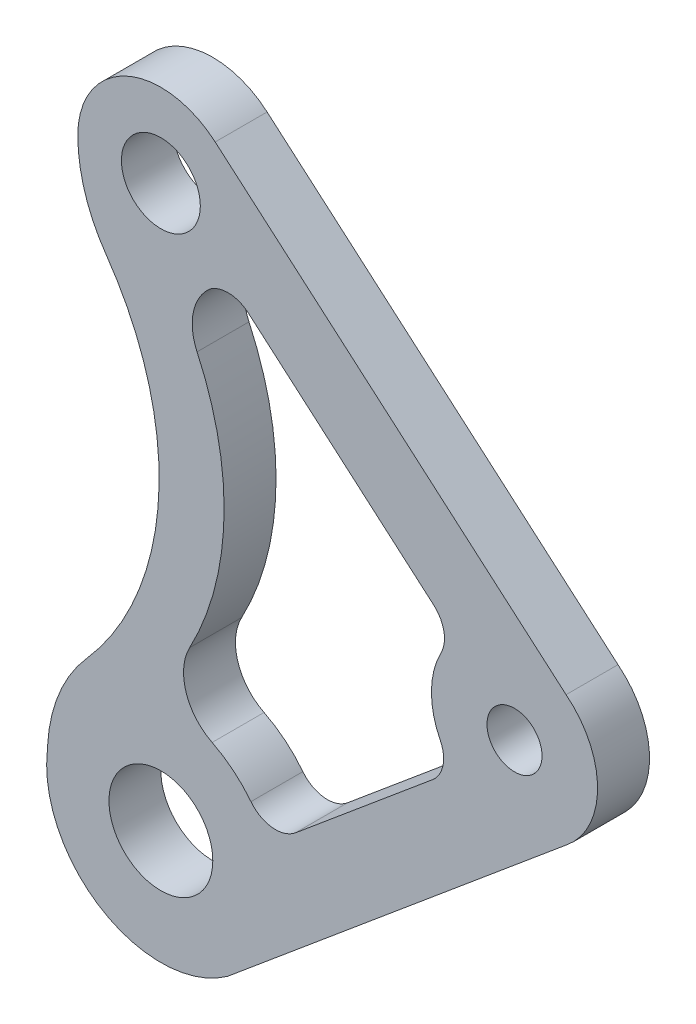
SolidWorks part; units mm, degrees
material "6061-T6 (SS)"
ref_plane "X-Y Datum" through (0, 0, 0) normal (0, 0, 1) x (1, 0, 0)
ref_plane "X-Z Datum" through (0, 0, 0) normal (0, 1, 0) x (1, 0, 0)
ref_plane "Y-Z Datum" through (0, 0, 0) normal (1, 0, 0) x (0, 0, -1)
sketch "Sketch1" plane through (0, 0, 0) normal (0, 0, 1) x (1, 0, 0)
  line L0 (0, 0) -> (0, 68.58) construction
  line L1 (0, 68.58) -> (43.2483, 31.2208) construction
  line L2 (43.2483, 31.2208) -> (0, 0) construction
  line L3 (-13.97, 0) -> (-10.16, 68.58)
  line L4 (6.6414, 76.2688) -> (49.5557, 39.1859)
  line L5 (49.5557, 23.2558) -> (8.1778, -11.3263)
  circle A0 centre (0, 0) radius 6.35
  circle A1 centre (43.2483, 31.2208) radius 3.3655
  circle A2 centre (0, 68.58) radius 4.826
  arc A3 (-10.16, 68.58) -> (6.6414, 76.2688) centre (0, 68.58) cw
  arc A4 (49.5557, 39.1859) -> (49.5557, 23.2558) centre (43.2483, 31.2208) cw
  arc A5 (8.1778, -11.3263) -> (-13.97, 0) centre (0, 0) cw
  point P16 (53.4083, 31.2208)
  dimension "D4" = 12.7
  dimension "D5" = 6.731
  dimension "D6" = 9.652
  dimension "D7" = 13.97
  dimension "D8" = 10.16
  dimension "D9" = 10.16
  dimension "D1" = 68.58
  dimension "D2" = 57.15
  dimension "D3" = 53.34
  dimension "D10" = 130.82
  dimension "D11" = 125.83
  dimension "D12" = 103.25
extrude "Boss-Extrude1" add sketch "Sketch1" along normal blind 6.35
sketch "Sketch2" plane through (0, 0, 6.35) normal (0, 0, 1) x (1, 0, 0)
  line L0 (-10.16, 68.58) -> (-13.97, 0) construction
  line L1 (-10.5128, 62.23) -> (-13.4408, 9.525)
  arc A0 (-10.5128, 62.23) -> (-13.4408, 9.525) centre (-35.7711, 37.1994) cw
  dimension "D3" = 35.56
  dimension "D1" = 6.35
  dimension "D2" = 9.525
extrude "Cut-Extrude1" cut sketch "Sketch2" against normal blind 6.35
fillet "Fillet1" radius 19.05 2 edges at (-10.5128, 62.23, 3.175) (-13.4408, 9.525, 3.175)
sketch "Sketch3" plane through (0, 0, 6.35) normal (0, 0, 1) x (1, 0, 0)
  line L2 (8.0877, 62.4306) -> (35.9845, 38.3245)
  line L3 (49.5557, 39.1859) -> (6.6414, 76.2688) construction
  line L6 (12.9992, 5.1168) -> (35.8725, 24.2335)
  arc A0 (35.9845, 38.3245) -> (35.8725, 24.2335) centre (43.2483, 31.2208) ccw
  arc A1 (-1.655, 13.8716) -> (12.9992, 5.1168) centre (0, 0) cw
  arc A3 (1.2017, 58.4913) -> (-1.655, 13.8716) centre (-27.8241, 37.9483) cw
  arc A6 (1.2017, 58.4913) -> (8.0877, 62.4306) centre (0, 68.58) ccw
  dimension "D1" = 10.16
  dimension "D2" = 10.16
  dimension "D3" = 13.97
  dimension "D6" = 6.7275
  dimension "D7" = 35.56
  dimension "D4" = 29.81
  dimension "D5" = 9.525
  dimension "D11" = 75.318
extrude "Cut-Extrude2" cut sketch "Sketch3" against normal blind 6.35
sketch3d "3DSketch1"
  line L0 (0, 68.58, 6.35) -> (0, 68.58, 0) construction
  line L1 (43.2483, 31.2208, 6.35) -> (43.2483, 31.2208, 0) construction
  point P0 (0, 68.58, 6.35)
  point P1 (43.2483, 31.2208, 6.35)
fillet "Fillet2" radius 3.81 4 edges at (35.9845, 38.3245, 3.175) (12.9992, 5.1168, 3.175) (35.8725, 24.2335, 3.175) (8.0877, 62.4306, 3.175)
fillet "Fillet4" radius 6.35 2 edges at (1.2017, 58.4913, 3.175) (-1.655, 13.8716, 3.175)
